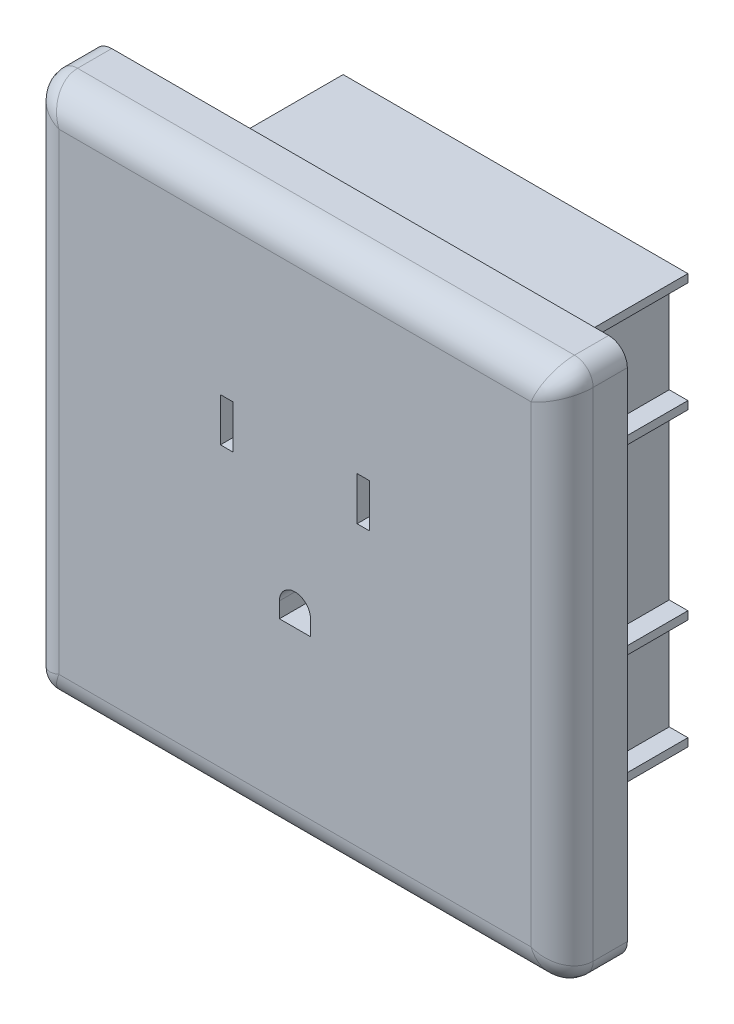
SolidWorks part; units mm, degrees
ref_plane "Front Plane" through (0, 0, 0) normal (0, 0, 1) x (1, 0, 0)
ref_plane "Top Plane" through (0, 0, 0) normal (0, 1, 0) x (1, 0, 0)
ref_plane "Right Plane" through (0, 0, 0) normal (1, 0, 0) x (0, 0, -1)
sketch "Sketch1" plane through (0, 0, 0) normal (0, 0, 1) x (1, 0, 0)
  line L1 (43, -43) -> (-43, -43)
  line L2 (43, -43) -> (43, 43)
  line L3 (43, 43) -> (-43, 43)
  line L4 (-43, -43) -> (-43, 43)
  line L5 (43, -43) -> (-43, 43) construction
  line L6 (43, 43) -> (-43, -43) construction
  point P0 (0, 0)
  dimension "D1" = 86
  dimension "D2" = 86
extrude "Boss-Extrude1" add sketch "Sketch1" along normal blind 10.5
sketch "Sketch2" plane through (0, 0, 0) normal (0, 0, 1) x (1, 0, 0)
  line L0 (-1000, 0) -> (49000, 0) construction
  circle A0 centre (-30, 0) radius 2
  circle A1 centre (30, 0) radius 2
  dimension "D2" = 30
  dimension "D3" = 4
  dimension "D4" = 4
  dimension "D1" = 30
extrude "Cut-Extrude1" cut sketch "Sketch2" along normal blind 5
sketch "Sketch3" plane through (0, 0, 0) normal (0, 0, 1) x (1, 0, 0)
  line L1 (-35, -35) -> (35, -35) construction
  line L2 (-35, -35) -> (-35, 35) construction
  line L3 (-35, 35) -> (35, 35) construction
  line L4 (35, -35) -> (35, 35) construction
  line L5 (-35, -35) -> (35, 35) construction
  line L6 (-35, 35) -> (35, -35) construction
  circle A0 centre (-35, 35) radius 1.9
  circle A1 centre (35, 35) radius 1.9
  circle A2 centre (35, -35) radius 1.9
  circle A3 centre (-35, -35) radius 1.9
  point P0 (0, 0)
  dimension "D3" = 3.8
  dimension "D4" = 3.8
  dimension "D5" = 3.8
  dimension "D6" = 3.8
  dimension "D1" = 70
  dimension "D2" = 70
extrude "Cut-Extrude2" cut sketch "Sketch3" along normal blind 5
sketch "Sketch4" plane through (0, 0, 0) normal (0, 0, -1) x (-1, 0, 0)
  line L1 (-24.75, -33) -> (24.75, -33)
  line L2 (-24.75, -33) -> (-24.75, 33)
  line L3 (-24.75, 33) -> (24.75, 33)
  line L4 (24.75, -33) -> (24.75, 33)
  line L5 (-24.75, -33) -> (24.75, 33) construction
  line L6 (-24.75, 33) -> (24.75, -33) construction
  point P0 (0, 0)
  dimension "D1" = 66
  dimension "D2" = 49.5
extrude "Boss-Extrude2" add sketch "Sketch4" along normal blind 25
sketch "Sketch5" plane through (0, 0, 0) normal (0, 0, -1) x (-1, 0, 0)
  line L13 (-24.75, 33) -> (-27.75, 33)
  line L14 (-24.75, 33) -> (-24.75, 14)
  line L15 (-24.75, 14) -> (-27.75, 14)
  line L16 (-27.75, 33) -> (-27.75, 14)
  dimension "D1" = 3
  dimension "D5" = 19
extrude "Boss-Extrude3" add sketch "Sketch5" along normal blind 25
sketch "Sketch6" plane through (0, 0, -25) normal (0, 0, -1) x (-1, 0, 0)
  line L0 (-27.75, 33) -> (-27.75, 14) construction
  line L1 (-27.75, 31.7) -> (-24.75, 31.7)
  line L2 (-27.75, 31.7) -> (-27.75, 15.3)
  line L3 (-27.75, 15.3) -> (-24.75, 15.3)
  line L4 (-24.75, 31.7) -> (-24.75, 15.3)
  line L5 (24.75, 33) -> (-27.75, 33) construction
  line L6 (-27.75, 14) -> (-24.75, 14) construction
  line L7 (-24.75, 14) -> (-24.75, -33) construction
  dimension "D1" = 1.3
  dimension "D2" = 1.3
extrude "Cut-Extrude3" cut sketch "Sketch6" against normal blind 25
mirror "Mirror1" about plane through (0, 0, 0) normal (1, 0, 0) of "Cut-Extrude3", "Boss-Extrude3"
mirror "Mirror2" about plane through (0, 0, 0) normal (0, 1, 0) of "Mirror1"
sketch "Sketch7" plane through (0, 0, 10.5) normal (0, 0, 1) x (1, 0, 0)
  line L1 (-12, 14) -> (-10, 14)
  line L2 (-12, 14) -> (-12, 7)
  line L3 (-12, 7) -> (-10, 7)
  line L4 (-10, 14) -> (-10, 7)
  dimension "D1" = 2
  dimension "D2" = 7
  dimension "D3" = 10
  dimension "D4" = 7
extrude "Cut-Extrude4" cut sketch "Sketch7" against normal blind 10
mirror "Mirror3" about plane through (0, 0, 0) normal (1, 0, 0) of "Cut-Extrude4"
sketch "Sketch8" plane through (0, 0, 10.5) normal (0, 0, 1) x (1, 0, 0)
  line L1 (-2.5, -10) -> (2.5, -10) construction
  line L2 (-2.5, -10) -> (-2.5, -12.5)
  line L3 (-2.5, -12.5) -> (2.5, -12.5)
  line L4 (2.5, -10) -> (2.5, -12.5)
  arc A0 (2.5, -10) -> (-2.5, -10) centre (0, -10) ccw
  dimension "D1" = 5
  dimension "D2" = 10
extrude "Cut-Extrude5" cut sketch "Sketch8" against normal blind 10
fillet "Fillet1" radius 3 4 edges at (-43, 43, 5.25) (-43, -43, 5.25) (43, 43, 5.25) (43, -43, 5.25)
fillet "Fillet3" radius 5 8 edges at (-42.1213, 42.1213, 10.5) (0, 43, 10.5) (42.1213, 42.1213, 10.5) (43, 0, 10.5) (42.1213, -42.1213, 10.5) (0, -43, 10.5) (-42.1213, -42.1213, 10.5) (-43, 0, 10.5)
